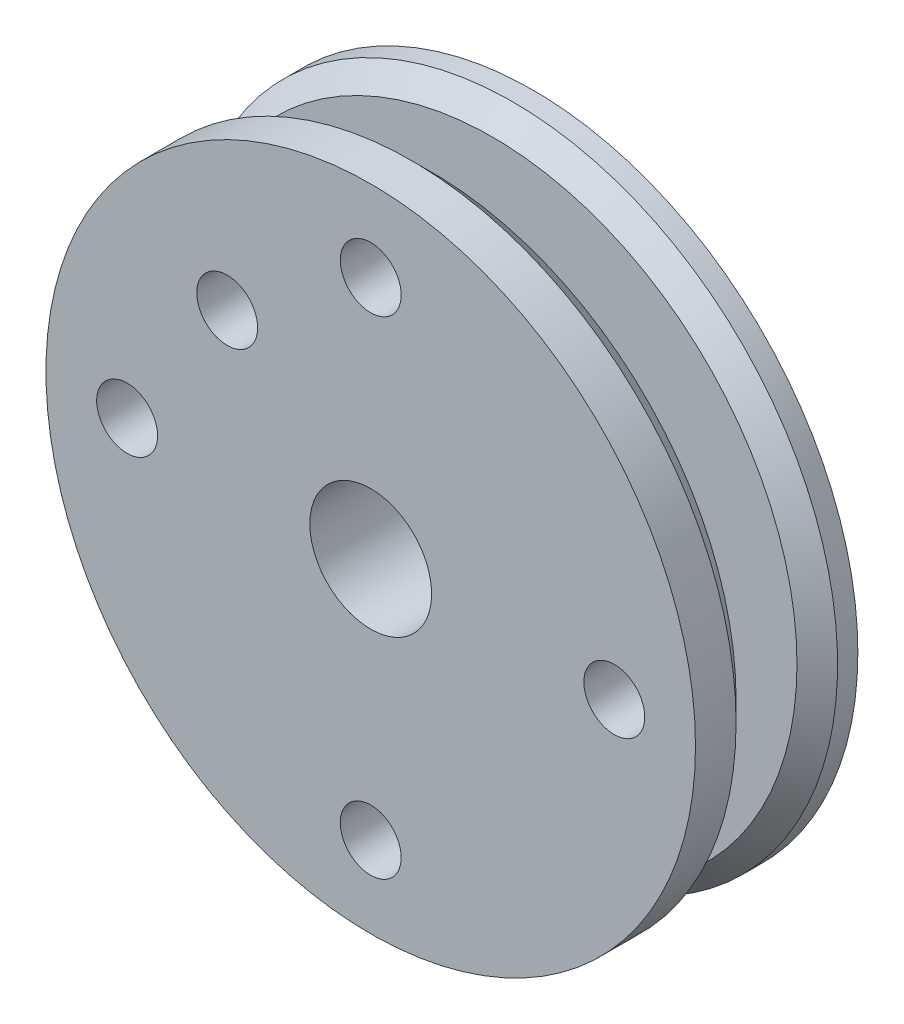
SolidWorks part; units mm, degrees
ref_plane "Ebene vorne" through (0, 0, 0) normal (0, 0, 1) x (1, 0, 0)
ref_plane "Ebene oben" through (0, 0, 0) normal (0, 1, 0) x (1, 0, 0)
ref_plane "Ebene rechts" through (0, 0, 0) normal (1, 0, 0) x (0, 0, -1)
sketch "Skizze2" plane through (0, 0, 0) normal (0, 0, 1) x (1, 0, 0)
  circle A0 centre (0, 0) radius 8
  dimension "D1" = 16
extrude "Aufsatz-Linear austragen1" add sketch "Skizze2" along normal blind 4
hole_wizard "Ø3.0 (3) Durchmesser Bohrung1" positions "Skizze4" profile "Skizze6" hole size "Ø3.0" standard "DIN" end condition through all
sketch "Skizze4" plane through (0, 0, 0) normal (0, 0, -1) x (-1, 0, 0)
  point P0 (0, 0)
sketch "Skizze6" plane through (0, 0, 0) normal (1, 0, 0) x (0, 1, 0)
  line L0 (0, 0) -> (0, 4)
  line L1 (0, 4) -> (1.5, 4)
  line L2 (1.5, 4) -> (1.5, 0)
  line L5 (1.5, 0) -> (0, 0)
  line L11 (0, -6.35) -> (0, 107.95) construction
  dimension "Bohrerdurchmesser" = 3
  dimension "Bohrungstiefe" = 4
sketch "Skizze8" plane through (0, 0, 4) normal (0, 0, 1) x (1, 0, 0)
  circle A0 centre (0, 0) radius 6 construction
  circle A1 centre (0, 6) radius 0.75
  circle A3 centre (6, 0) radius 0.75
  circle A4 centre (0, -6) radius 0.75
  circle A5 centre (-6, 0) radius 0.75
  dimension "D1" = 4
  dimension "D2" = 1.5
  dimension "D3" = 12
sketch "Skizze9" plane through (0, 0, 0) normal (0, 1, 0) x (1, 0, 0)
  line L0 (0, 0) -> (0, -4) construction
  line L1 (-8, -4) -> (8, -4) construction
  line L2 (-4.5, -2.5) -> (-8, -2.5)
  line L3 (-8, 0) -> (-8, -4) construction
  line L6 (-8, -1) -> (-4.5, -1)
  line L7 (8, 0) -> (-8, 0) construction
  line L12 (-8, 0) -> (-8, -4) construction
  line L13 (-8, -2.5) -> (-8, -1)
  arc A5 (-4.5, -2.5) -> (-4.5, -1) centre (-4.5, -1.75) ccw
  dimension "D2" = 1.5
  dimension "D3" = 1
  dimension "D1" = 3.5
revolve "Schnitt-Rotation2" cut sketch "Skizze9" angle 360 about L0
extrude "Aufsatz-Linear austragen2" add sketch "Skizze8" along normal blind 2
hole_wizard "Ø1.5 (1.5) Durchmesser Bohrung1" positions "Skizze13" profile "Skizze14" hole size "Ø1.5" standard "DIN" end condition through all
sketch "Skizze13" plane through (0, 0, 0) normal (0, 0, 1) x (1, 0, 0)
  line L1 (0, 0) -> (-3.5355, 3.5355) construction
  point P0 (-3.5355, 3.5355)
  dimension "D1" = 45
  dimension "D2" = 5
sketch "Skizze14" plane through (-3.5355, 3.5355, 0) normal (1, 0, 0) x (0, 1, 0)
  line L0 (0, 0) -> (0, 6)
  line L1 (0, 6) -> (0.75, 6)
  line L2 (0.75, 6) -> (0.75, 0)
  line L5 (0.75, 0) -> (0, 0)
  line L11 (0, -6.35) -> (0, 107.95) construction
  dimension "Bohrerdurchmesser" = 1.5
  dimension "Bohrungstiefe" = 6
chamfer "Fase1" distance 0.5 angle 45 2 edges at (-8, 0, 2.5) (-8, 0, 1)
chamfer "Fase2" distance 0.3 angle 45 4 edges at (0.75, 6, 6) (6.75, 0, 6) (0.75, -6, 6) (-5.25, 0, 6)
ref_plane "Ebene1" through (0, 0, 2) normal (0, 0, 1) x (1, 0, 0)
sketch "Skizze16" plane through (0, 0, 2) normal (0, 0, 1) x (1, 0, 0)
  circle A0 centre (0, 0) radius 6 construction
  circle A1 centre (0, 6) radius 0.75
  circle A3 centre (6, 0) radius 0.75
  circle A4 centre (0, -6) radius 0.75
  circle A5 centre (-6, 0) radius 0.75
  dimension "D1" = 4
  dimension "D2" = 1.5
  dimension "D3" = 12
extrude "Schnitt-Linear austragen1" cut sketch "Skizze16" along normal blind 5
